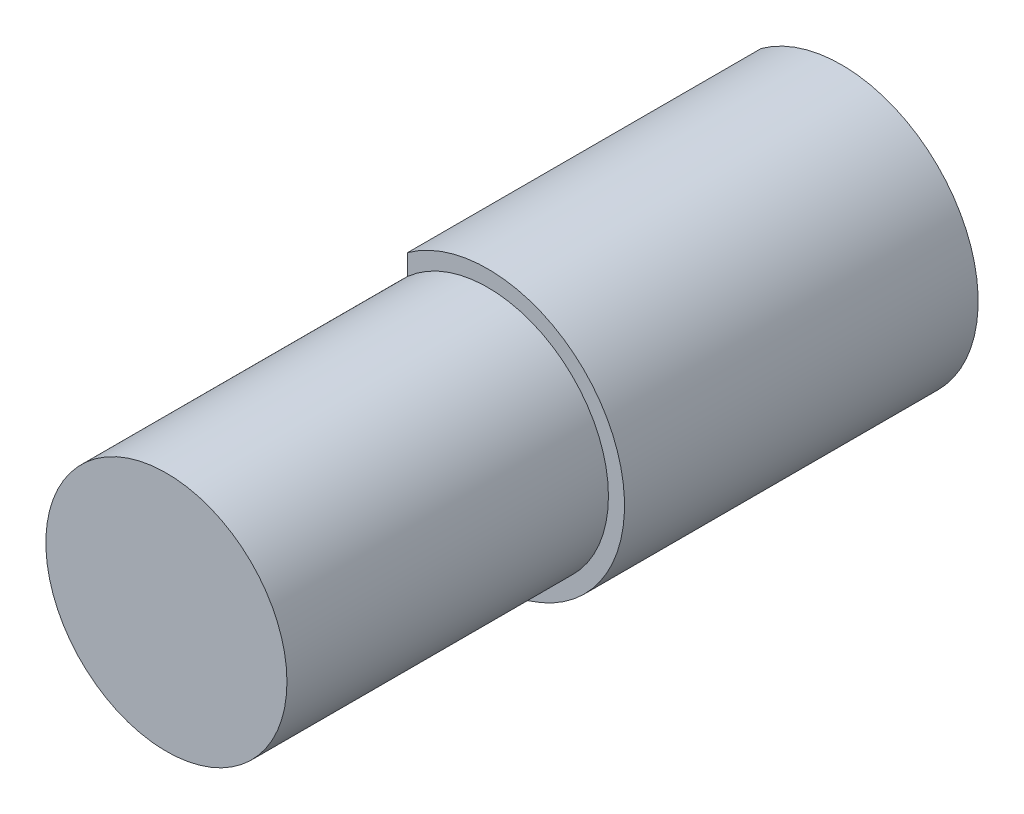
SolidWorks part; units mm, degrees
ref_plane "Front Plane" through (0, 0, 0) normal (0, 0, 1) x (1, 0, 0)
ref_plane "Top Plane" through (0, 0, 0) normal (0, 1, 0) x (1, 0, 0)
ref_plane "Right Plane" through (0, 0, 0) normal (1, 0, 0) x (0, 0, -1)
sketch "Sketch1" plane through (0, 0, 0) normal (0, 0, 1) x (1, 0, 0)
  line L0 (-2.5, 3.4369) -> (-2.5, -3.4369)
  arc A0 (-2.5, -3.4369) -> (-2.5, 3.4369) centre (0, 0) ccw
  dimension "D1" = 2.5
  dimension "D2" = 8.5
extrude "Boss-Extrude1" add sketch "Sketch1" along normal blind 10
sketch "Sketch2" plane through (0, 0, 10) normal (0, 0, 1) x (1, 0, 0)
  circle A0 centre (0, 0) radius 4.25
extrude "Boss-Extrude2" add sketch "Sketch2" along normal blind 20
sketch "Sketch3" plane through (0, 0, 0) normal (0, 0, -1) x (-1, 0, 0)
  line L1 (2.5, -3.4369) -> (2.5, 3.4369)
  line L2 (2.5, -3.4369) -> (2.5, 3.4369)
  arc A1 (2.5, 3.4369) -> (2.5, -3.4369) centre (0, 0) ccw
  arc A2 (2.5, 3.4369) -> (2.5, -3.4369) centre (0, 0) ccw
  dimension "D1" = 0
extrude "Boss-Extrude3" add sketch "Sketch3" along normal blind 1
sketch "Sketch5" plane through (0, 0, 30) normal (0, 0, 1) x (1, 0, 0)
  circle A0 centre (0, 0) radius 3.75
  circle A1 centre (0, 0) radius 4.25
  circle A2 centre (0, 0) radius 4.25
  dimension "D1" = 0
  dimension "D2" = 0.5
extrude "Cut-Extrude1" cut sketch "Sketch5" against normal up to surface (20 mm away) up to face at (-2.5, 3.4369, 10)
sketch "Sketch6" plane through (0, 0, 30) normal (0, 0, 1) x (1, 0, 0)
  circle A1 centre (0, 0) radius 3.75
  circle A2 centre (0, 0) radius 3.75
  dimension "D1" = 0
extrude "Cut-Extrude2" cut sketch "Sketch6" against normal blind 10
